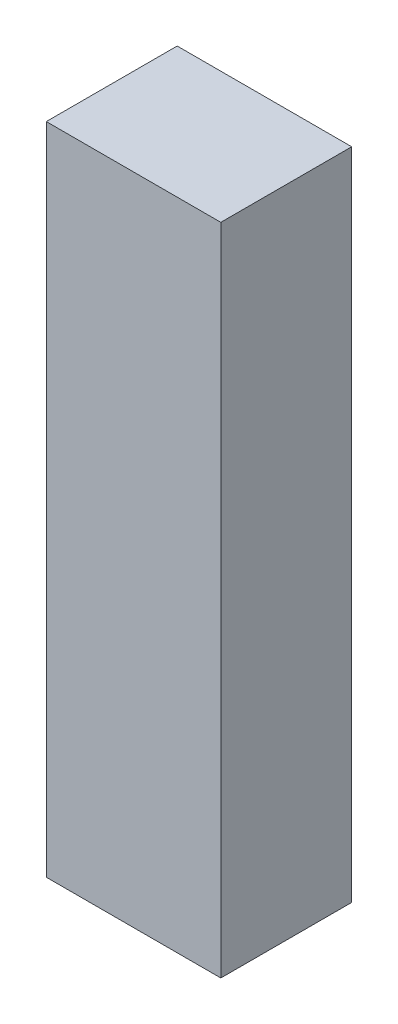
SolidWorks part; units mm, degrees
ref_plane "前视基准面" through (0, 0, 0) normal (0, 0, 1) x (1, 0, 0)
ref_plane "上视基准面" through (0, 0, 0) normal (0, 1, 0) x (1, 0, 0)
ref_plane "右视基准面" through (0, 0, 0) normal (1, 0, 0) x (0, 0, -1)
other "Configuration Table"
sketch "草图1" plane through (0, 0, 0) normal (0, 1, 0) x (1, 0, 0)
  line L1 (-40, -30) -> (40, -30)
  line L2 (-40, -30) -> (-40, 30)
  line L3 (-40, 30) -> (40, 30)
  line L4 (40, -30) -> (40, 30)
  line L5 (-40, -30) -> (40, 30) construction
  line L6 (-40, 30) -> (40, -30) construction
  point P0 (0, 0)
extrude "凸台-拉伸1" add sketch "草图1" along normal blind 300
